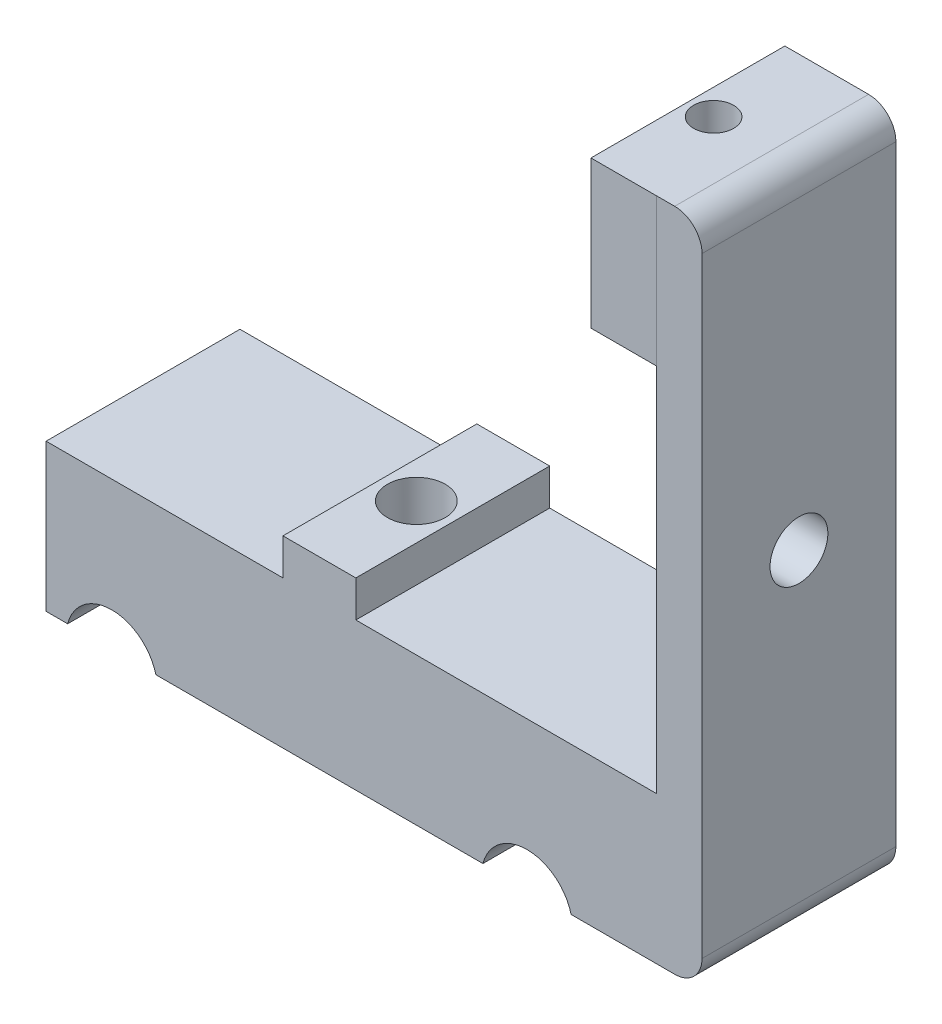
SolidWorks part; units mm, degrees
ref_plane "Front Plane" through (0, 0, 0) normal (0, 0, 1) x (1, 0, 0)
ref_plane "Top Plane" through (0, 0, 0) normal (0, 1, 0) x (1, 0, 0)
ref_plane "Right Plane" through (0, 0, 0) normal (1, 0, 0) x (0, 0, -1)
sketch "Sketch2" plane through (0, 0, 0) normal (0, 0, 1) x (1, 0, 0)
  line L0 (10.1, 0) -> (-10.1, 0)
  line L1 (-10.1, 0) -> (-10.1, 1.7099)
  line L2 (-10.1, 1.7099) -> (-6.2548, 7)
  line L3 (-6.2548, 7) -> (6.2548, 7)
  line L4 (0, 7) -> (0, 0)
  line L5 (0, 0) -> (0, 9.2516) construction
  line L6 (10.1, 1.7099) -> (6.2548, 7)
  line L7 (10.1, 0) -> (10.1, 1.7099)
  dimension "D1" = 20.2
  dimension "D2" = 7
extrude "Boss-Extrude1" add sketch "Sketch2" along normal blind 10.8 contours L4 L3 L2 L1 L0 | L0 L7 L6 L3 L4 region at (4.4168, 3.2082, 0) region at (-4.4168, 3.2082, 0)
sketch "Sketch4" plane through (0, 0, 0) normal (0, 0, 1) x (1, 0, 0)
  line L0 (-4, 0) -> (-4, -4.8)
  line L1 (10.1, 0) -> (-10.1, 0) construction
  line L2 (-4, -4.8) -> (-30, -4.8)
  line L3 (-30, -4.8) -> (-30, -29.8)
  line L4 (-30, -29.8) -> (30, -29.8)
  line L5 (0, 0) -> (0, -29.8) construction
  line L6 (0, -29.8) -> (0, 0)
  line L7 (4, 0) -> (-4, 0)
  line L8 (0, 0) -> (0, -30.5381) construction
  line L9 (30, -4.8) -> (30, -29.8)
  line L10 (4, -4.8) -> (30, -4.8)
  line L11 (4, 0) -> (4, -4.8)
  line L13 (-30, -20.98) -> (30, -20.98)
  line L14 (-30, -20.98) -> (-30, -23.48)
  line L15 (-30, -23.48) -> (30, -23.48)
  line L16 (30, -20.98) -> (30, -23.48)
  dimension "D1" = 4.8
  dimension "D2" = 4
  dimension "D3" = 25
  dimension "D4" = 60
  dimension "D6" = 8.82
extrude "Boss-Extrude2" add sketch "Sketch4" along normal mid plane 21.28 contours L6 L7 L0 L2 L3 L4 | L11 L7 L6 L4 L9 L10 region at (-14.5054, -12.4909, 0) region at (14.5054, -12.4909, 0)
sketch "Sketch5" plane through (0, 0, 0) normal (0, 0, 1) x (1, 0, 0)
  line L0 (-29.791, -22.2274) -> (26.9734, -22.2274) construction
  line L3 (0, -20.98) -> (0, 7) construction
  line L5 (-6.2548, 7) -> (6.2548, 7) construction
  line L20 (-30, -20.98) -> (30, -20.98) construction
  circle A0 centre (-22.791, -22.2274) radius 5
  circle A1 centre (22.791, -22.2274) radius 5
  dimension "D1" = 7
extrude "Cut-Extrude1" cut sketch "Sketch5" along normal through all both and the other way through all
fillet "Fillet1" radius 1 6 edges at (-10.1, 0, 5.4) (-10.1, 1.7099, 5.4) (-6.2548, 7, 5.4) (6.2548, 7, 5.4) (10.1, 0, 5.4) (10.1, 1.7099, 5.4)
sketch "Sketch6" plane through (30, 0, 0) normal (1, 0, 0) x (0, 0, -1)
  line L0 (-10.64, -20.98) -> (10.64, -20.98) construction
  line L1 (-10.64, -4.8) -> (10.64, -4.8)
  line L2 (-10.64, -4.8) -> (-10.64, -20.98)
  line L3 (-10.64, -20.98) -> (10.64, -20.98)
  line L4 (10.64, -4.8) -> (10.64, -20.98)
extrude "Boss-Extrude3" add sketch "Sketch6" along normal blind 12
sketch "Sketch7" plane through (0, -4.8, 0) normal (0, 1, 0) x (1, 0, 0)
  line L0 (4, -10.64) -> (42, -10.64) construction
  line L1 (42, 10.6413) -> (37, 10.6413)
  line L2 (42, 10.6413) -> (42, -10.64)
  line L3 (42, -10.64) -> (37, -10.64)
  line L4 (37, 10.6413) -> (37, -10.64)
  dimension "D1" = 5
extrude "Boss-Extrude4" add sketch "Sketch7" along normal blind 56.83
sketch "Sketch8" plane through (37, 0, 0) normal (-1, 0, 0) x (0, 0, 1)
  line L0 (-10.6413, 52.03) -> (-10.6413, -4.8) construction
  line L1 (10.643, 52.03) -> (-10.6413, 52.03)
  line L2 (10.643, 52.03) -> (10.643, 35.85)
  line L3 (10.643, 35.85) -> (-10.6413, 35.85)
  line L4 (-10.6413, 52.03) -> (-10.6413, 35.85)
  dimension "D1" = 16.18
extrude "Boss-Extrude5" add sketch "Sketch8" along normal blind 7.19
fillet "Fillet3" radius 3 2 edges at (42, 52.03, -0.0007) (42, -20.98, 0)
sketch "Sketch9" plane through (0, -20.98, 0) normal (0, -1, 0) x (1, 0, 0)
  line L0 (27.6329, 0) -> (27.6329, 10.8) construction
  line L2 (27.6329, 10.64) -> (39, 10.64) construction
  circle A0 centre (32.6329, 0) radius 2.2
  dimension "D1" = 5
  dimension "D2" = 10.64
extrude "Cut-Extrude2" cut sketch "Sketch9" against normal through all
sketch "Sketch10" plane through (0, -20.98, 0) normal (0, -1, 0) x (1, 0, 0)
  line L2 (-17.9491, 0) -> (-17.9491, 10.8) construction
  line L3 (-17.9491, 10.64) -> (17.9491, 10.64) construction
  circle A0 centre (0.0009, 0) radius 3.175
  dimension "D1" = 10.64
  dimension "D3" = 6.35
  dimension "D2" = 17.95
extrude "Cut-Extrude3" cut sketch "Sketch10" against normal through all
sketch "Sketch11" plane through (0, 0, 10.8) normal (0, 0, 1) x (1, 0, 0)
  line L0 (9.1, 0) -> (-9.1, 0) construction
  line L1 (-12.6098, 8.9215) -> (12.3675, 8.9215)
  line L2 (-12.6098, 8.9215) -> (-12.6098, -0.8)
  line L3 (-12.6098, -0.8) -> (12.3675, -0.8)
  line L4 (12.3675, 8.9215) -> (12.3675, -0.8)
  dimension "D1" = 0.8
extrude "Cut-Extrude4" cut sketch "Sketch11" against normal through all
sketch "Sketch12" plane through (42, 0, 0) normal (1, 0, 0) x (0, 0, -1)
  line L1 (10.6413, 49.03) -> (-10.64, 49.03) construction
  circle A0 centre (0, 15.525) radius 3.175
  dimension "D1" = 33.505
extrude "Cut-Extrude5" cut sketch "Sketch12" against normal through all
